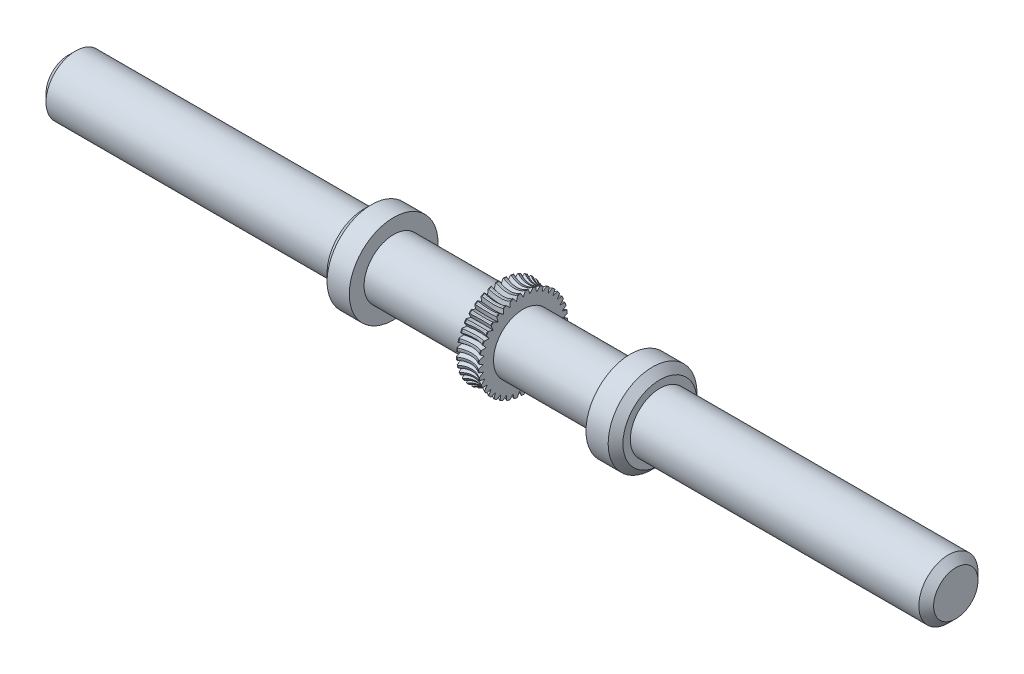
SolidWorks part; units mm, degrees
material "Plain Carbon Steel"
ref_plane "Front Plane" through (0, 0, 0) normal (0, 0, 1) x (1, 0, 0)
ref_plane "Top Plane" through (0, 0, 0) normal (0, 1, 0) x (1, 0, 0)
ref_plane "Right Plane" through (0, 0, 0) normal (1, 0, 0) x (0, 0, -1)
sketch "Sketch1" plane through (0, 0, 0) normal (0, 0, 1) x (1, 0, 0)
  line L0 (-10, 3) -> (10, 3)
  line L1 (-10, 3) -> (-10, 2)
  line L2 (-30, 0) -> (30, 0)
  line L3 (-30, 0) -> (-30, 2)
  line L4 (-30, 2) -> (-10, 2)
  line L5 (30, 0) -> (30, 2)
  line L6 (10, 3) -> (10, 2)
  line L7 (10, 2) -> (30, 2)
  line L8 (0, 0) -> (67.2135, 0) construction
  line L9 (0, 0) -> (0, 19.6593) construction
  dimension "D1" = 6
  dimension "D2" = 20
  dimension "D3" = 20
  dimension "D4" = 20
  dimension "D5" = 4
revolve "Revolve1" add sketch "Sketch1" angle 360 about L8
chamfer "Chamfer1" distance 0.5 angle 45 4 edges at (30, 0, 2) (10, 0, 3) (-10, 0, 3) (-30, 0, 2)
sketch "Sketch2" plane through (0, 0, 0) normal (1, 0, 0) x (0, 0, -1)
  line L0 (0, 0) -> (0, 4) construction
  line L1 (9.9899, 4) -> (-9.864, 4) construction
  line L2 (0.1562, 2.7705) -> (0, 2.5)
  line L3 (0, 2.5) -> (-0.1562, 2.7705)
  line L4 (-1.1508, 4) -> (1.1508, 4)
  line L5 (-0.1562, 2.7705) -> (-1.1508, 2.7705)
  line L6 (0.1562, 2.7705) -> (1.1508, 2.7705)
  line L7 (1.1508, 2.7705) -> (1.1508, 4)
  line L8 (-1.1508, 2.7705) -> (-1.1508, 4)
  line L9 (0, 0) -> (-6.9817, 0) construction
  line L10 (5.645, 3) -> (-5.97, 3) construction
  circle A0 centre (0, 0) radius 3 construction
  circle A1 centre (0, 0) radius 2.5 construction
  dimension "D1" = 60
  dimension "D2" = 3
  dimension "D3" = 2.459
  dimension "D4" = 1
revolve "Cut-Revolve1" cut sketch "Sketch2" angle 360 about L1
pattern_circular "CirPattern1" count 37 over 360 about axis through (0, 0, 0) along (-1, 0, 0) of "Cut-Revolve1"
sketch "Sketch3" plane through (0, 0, 0) normal (0, 0, 1) x (1, 0, 0)
  line L0 (29.5, 2) -> (10, 2) construction
  line L1 (8, 3) -> (0.75, 3)
  line L2 (8, 3) -> (8, 2)
  line L3 (8, 2) -> (0.75, 2)
  line L4 (0.75, 3) -> (0.75, 2)
  line L5 (-0.75, 3) -> (-8, 3)
  line L6 (-0.75, 3) -> (-0.75, 2)
  line L7 (-0.75, 2) -> (-8, 2)
  line L8 (-8, 3) -> (-8, 2)
  line L9 (0, 0) -> (0, 15.3026) construction
  line L10 (0, 0) -> (-13.7134, 0) construction
  line L11 (9.5, 3) -> (1.118, 3) construction
  dimension "D1" = 1.5
  dimension "D2" = 16
revolve "Cut-Revolve2" cut sketch "Sketch3" angle 360 about L10
